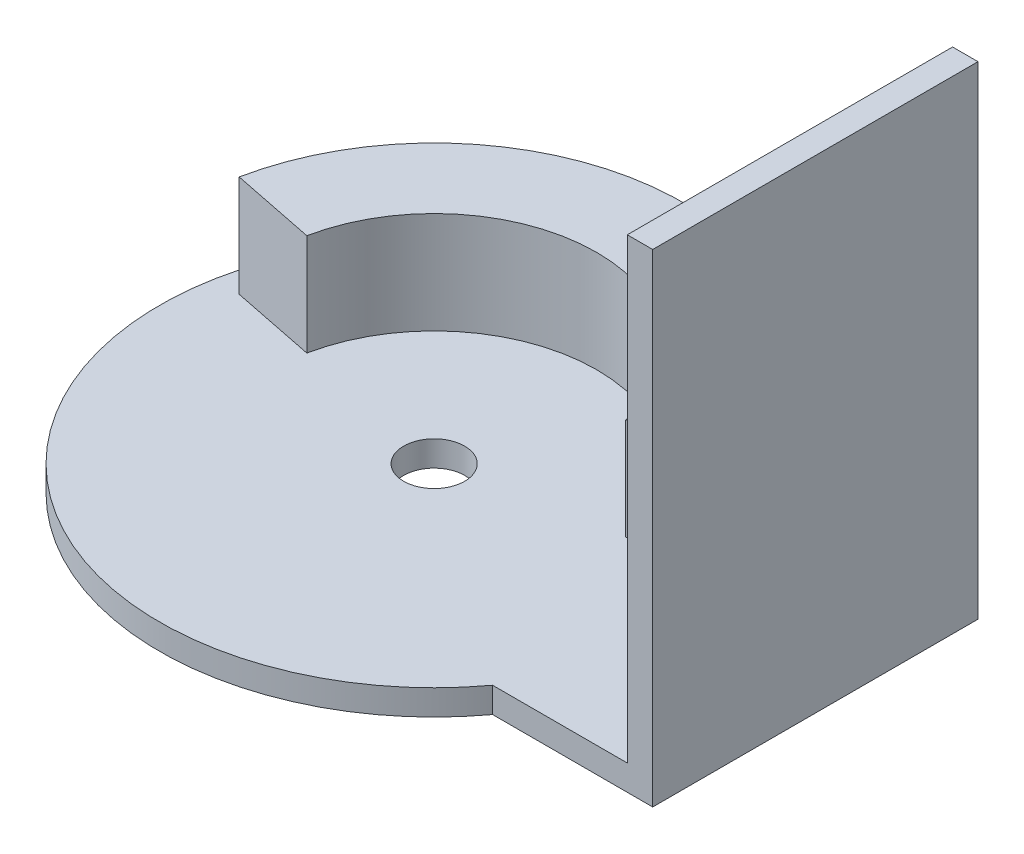
SolidWorks part; units mm, degrees
ref_plane "Front Plane" through (0, 0, 0) normal (0, 0, 1) x (1, 0, 0)
ref_plane "Top Plane" through (0, 0, 0) normal (0, 1, 0) x (1, 0, 0)
ref_plane "Right Plane" through (0, 0, 0) normal (1, 0, 0) x (0, 0, -1)
sketch "Sketch1" plane through (0, 0, 0) normal (0, 1, 0) x (1, 0, 0)
  line L0 (-55, 0) -> (55, 0) construction
  line L1 (-24.0173, 4.8395) -> (-20.7184, 21.2108) construction
  line L2 (-24.0173, 4.8395) -> (-15.6847, 3.1605)
  line L3 (0, -55) -> (0, 55) construction
  line L4 (24.0173, 4.8395) -> (15.6847, 3.1605)
  line L5 (-23.9844, 5) -> (23.9844, 5) construction
  circle A0 centre (0, 0) radius 16 construction
  circle A1 centre (0, 0) radius 24.5 construction
  arc A2 (-24.0173, 4.8395) -> (24.0173, 4.8395) centre (0, 0) cw
  arc A3 (-15.6847, 3.1605) -> (15.6847, 3.1605) centre (0, 0) cw
  point P20 (-19.851, 4)
  dimension "D1" = 32
  dimension "D2" = 49
  dimension "D3" = 1
  dimension "D4" = 5
extrude "Boss-Extrude1" add sketch "Sketch1" along normal blind 10 contours A2 L4 A3 L2
sketch "Sketch2" plane through (0, 0, 0) normal (0, -1, 0) x (1, 0, 0)
  line L1 (37.5, -16) -> (37.5, 16)
  line L3 (21.7486, -16) -> (37.5, -16)
  line L5 (21.7486, 16) -> (37.5, 16)
  line L6 (0, -55) -> (0, 55) construction
  circle A1 centre (0, 0) radius 27 construction
  circle A2 centre (0, 0) radius 3
  arc A3 (0, -27) -> (0, 27) centre (0, 0) cw
  circle A4 centre (0, 0) radius 16 construction
  arc A5 (21.7486, -16) -> (0, -27) centre (0, 0) cw
  arc A6 (0, 27) -> (21.7486, 16) centre (0, 0) cw
  dimension "D1" = 54
  dimension "D2" = 6
  dimension "D3" = 37.5
extrude "Boss-Extrude2" add sketch "Sketch2" along normal blind 2.5
sketch "Sketch4" plane through (0, 0, 0) normal (0, 1, 0) x (1, 0, 0)
  line L0 (37.5, -16) -> (21.7486, -16) construction
  line L1 (37.5, -16) -> (35, -16)
  line L2 (37.5, -16) -> (37.5, 16)
  line L3 (37.5, 16) -> (35, 16)
  line L4 (35, -16) -> (35, 16)
  line L5 (21.7486, 16) -> (37.5, 16) construction
  dimension "D1" = 2.5
  dimension "D2" = 35
extrude "Boss-Extrude3" add sketch "Sketch4" along normal blind 45
